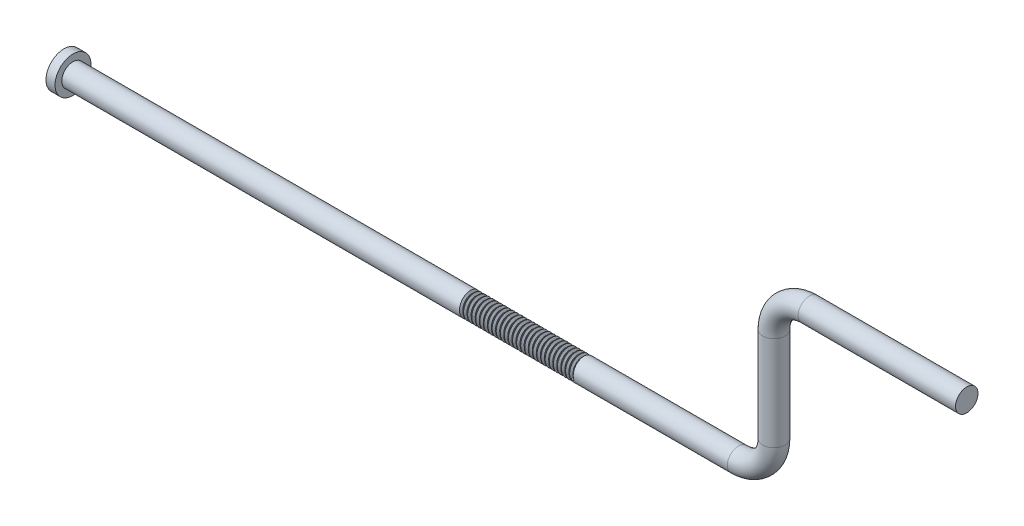
SolidWorks part; units mm, degrees
material "1023 Carbon Steel Sheet (SS)"
ref_plane "Front" through (0, 0, 0) normal (0, 0, 1) x (1, 0, 0)
ref_plane "Top" through (0, 0, 0) normal (0, 1, 0) x (1, 0, 0)
ref_plane "Right" through (0, 0, 0) normal (1, 0, 0) x (0, 0, -1)
sketch "Sketch1" plane through (0, 0, 0) normal (0, 0, 1) x (1, 0, 0)
  line L0 (-35.5632, 0) -> (24.4368, 0)
  line L1 (55, 0) -> (-55, 0) construction
  line L2 (32.3103, 7.8735) -> (32.3103, 28.8735)
  line L3 (40.1838, 36.747) -> (75.1838, 36.747)
  arc A0 (24.4368, 0) -> (32.3103, 7.8735) centre (24.4368, 7.8735) ccw
  arc A1 (40.1838, 36.747) -> (32.3103, 28.8735) centre (40.1838, 28.8735) ccw
  point P8 (24.4368, 0)
  point P12 (32.3103, 28.8735)
  dimension "D3" = 15.747
  dimension "D4" = 15.747
  dimension "D1" = 60
  dimension "D2" = 35
  dimension "D5" = 21
ref_plane "Plane1" through (-35.5632, 0, 0) normal (1, 0, 0) x (0, 0, -1)
sketch "Sketch3" plane through (-35.5632, 0, 0) normal (1, 0, 0) x (0, 0, -1)
  circle A0 centre (0, 0) radius 2.5
  point P0 (0, 0)
sweep "Sweep1" add profiles "Sketch3" path "Sketch1"
sketch "Sketch4" plane through (0, 0, 0) normal (0, 0, 1) x (1, 0, 0)
  line L1 (75.1838, 39.247) -> (40.1838, 39.247) construction
  line L3 (75.1838, 39.247) -> (40.1838, 39.247)
  line L4 (40.1838, 39.247) -> (40.1838, 45.747)
  line L5 (50.4866, 45.747) -> (73.4428, 45.747)
  line L6 (78.4428, 40.747) -> (78.4428, 39.247)
  line L7 (75.1838, 39.247) -> (40.1838, 39.247)
  line L8 (75.1838, 39.247) -> (75.1838, 36.747)
  line L10 (75.1838, 34.247) -> (75.1838, 39.247) construction
  line L12 (75.1838, 36.747) -> (78.4428, 36.747)
  line L14 (78.4428, 36.747) -> (78.4428, 39.247)
  line L16 (40.1838, 36.747) -> (78.4428, 36.747) construction
  line L17 (40.1838, 39.247) -> (40.1838, 34.247) construction
  arc A0 (46.4512, 47.7948) -> (40.1838, 45.747) centre (43.652, 45.747) ccw
  arc A2 (78.4428, 40.747) -> (73.4428, 45.747) centre (73.4428, 40.747) ccw
  arc A3 (50.4866, 45.747) -> (46.4512, 47.7948) centre (50.4866, 50.747) cw
  point P15 (47.1203, 45.747)
  dimension "D2" = 5
  dimension "D3" = 5
  dimension "D1" = 6.5
ref_plane "Plane2" through (-20.5632, 0, 0) normal (1, 0, 0) x (0, 0, -1)
sketch "Sketch5" plane through (-20.5632, 0, 0) normal (1, 0, 0) x (0, 0, -1)
  circle A0 centre (0, 0) radius 2.5 construction
  circle A1 centre (0, 0) radius 2.5
thread "Thread2" pitch 0.9071 method cut profile "Thread Profile2" start angle 0, offset 0, length 25, pitch 0.9071, diameter 5
ref_plane "Plane4" through (-35.5632, 0, -2.5) normal (0, -1, 0) x (0, 0, -1)
sketch "Thread Profile2" plane through (-35.5632, 0, -2.5) normal (0, -1, 0) x (0, 0, -1)
  line L0 (0, 0) -> (0, 0.9071) construction
  line L11 (0, 0) -> (0, 0.7937)
  line L12 (0, 0.7937) -> (-0.491, 0.5103)
  line L13 (-0.491, 0.5103) -> (-0.491, 0.2835)
  line L15 (-0.491, 0.2835) -> (0, 0)
  line L17 (-0.491, 0.3969) -> (0, 0.3969) construction
  point P2 (0, 0)
  dimension "Pitch" = 0.9071
  dimension "Profile_Angle" = 60
  dimension "Profile_Land" = 0.2268
  dimension "Profile_Height" = 0.491
sketch "Sketch17" plane through (-35.5632, 0, 0) normal (1, 0, 0) x (0, 0, -1)
  circle A0 centre (0, 0) radius 2.5 construction
  circle A1 centre (0, 0) radius 2.5
extrude "Boss-Extrude1" add sketch "Sketch17" against normal blind 90
sketch "Sketch20" plane through (-125.5632, 0, 0) normal (-1, 0, 0) x (0, 0, 1)
  circle A0 centre (0, 0) radius 4
  dimension "D1" = 8
extrude "Boss-Extrude2" add sketch "Sketch20" against normal blind 2
